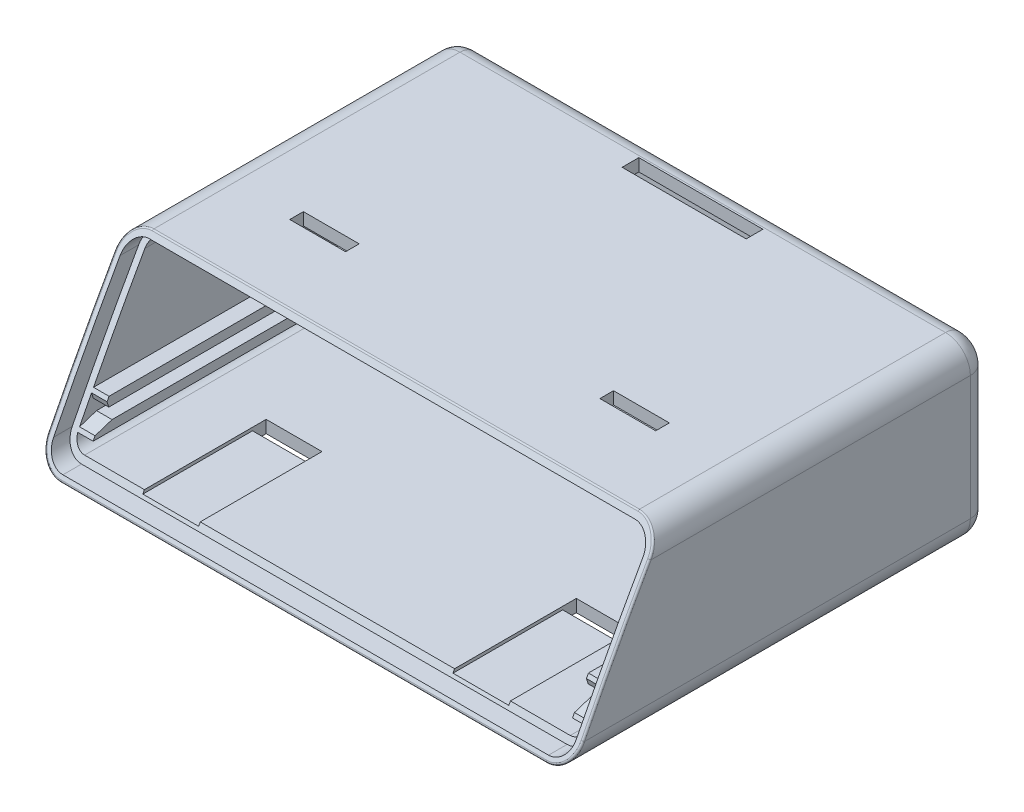
SolidWorks part; units mm, degrees
ref_plane "Front Plane" through (0, 0, 0) normal (0, 0, 1) x (1, 0, 0)
ref_plane "Top Plane" through (0, 0, 0) normal (0, 1, 0) x (1, 0, 0)
ref_plane "Right Plane" through (0, 0, 0) normal (1, 0, 0) x (0, 0, -1)
sketch "Sketch1" plane through (0, 0, 0) normal (0, 1, 0) x (1, 0, 0)
  line L1 (-43.14, -33.75) -> (43.14, -33.75)
  line L2 (-43.14, -33.75) -> (-43.14, 33.75)
  line L3 (-43.14, 33.75) -> (43.14, 33.75)
  line L4 (43.14, -33.75) -> (43.14, 33.75)
  line L5 (-43.14, -33.75) -> (43.14, 33.75) construction
  line L6 (-43.14, 33.75) -> (43.14, -33.75) construction
  point P0 (0, 0)
  dimension "D1" = 67.5
  dimension "D2" = 86.28
extrude "Boss-Extrude1" add sketch "Sketch1" along normal blind 28
fillet "Fillet1" radius 4 4 edges at (43.14, 28, 0) (43.14, 0, 0) (-43.14, 0, 0) (-43.14, 28, 0)
shell "Shell1" thickness 2
sketch "Sketch2" plane through (-43.14, 0, 0) normal (-1, 0, 0) x (0, 0, 1)
  line L0 (-33.75, 28) -> (33.75, 28) construction
  line L1 (18.75, 28) -> (33.75, 28)
  line L2 (33.75, 28) -> (33.75, 0)
  arc A0 (33.75, 0) -> (18.75, 28) centre (-392.2189, -210.1797) ccw
  dimension "D1" = 15
  dimension "D2" = 475
extrude "Cut-Extrude1" cut sketch "Sketch2" against normal through all
sketch "Sketch3" plane through (0, 0, -33.75) normal (0, 0, -1) x (-1, 0, 0)
  line L0 (-7.15, 18.7) -> (7.15, 18.7)
  line L1 (-6.95, 18.5) -> (6.95, 18.5) construction
  line L2 (-6.95, 18.5) -> (-6.95, 2.2) construction
  line L3 (-6.95, 2.2) -> (6.95, 2.2) construction
  line L4 (6.95, 18.5) -> (6.95, 2.2) construction
  line L5 (7.15, 18.7) -> (7.15, 2)
  line L6 (-7.15, 2) -> (7.15, 2)
  line L7 (-7.15, 18.7) -> (-7.15, 2)
  line L8 (27.25, 17.2) -> (38.3, 17.2)
  line L9 (27.45, 17) -> (38.1, 17) construction
  line L10 (27.45, 17) -> (27.45, 3.35) construction
  line L11 (27.45, 3.35) -> (38.1, 3.35) construction
  line L12 (38.1, 17) -> (38.1, 3.35) construction
  line L13 (38.3, 17.2) -> (38.3, 3.15)
  line L14 (27.25, 3.15) -> (38.3, 3.15)
  line L15 (27.25, 17.2) -> (27.25, 3.15)
  dimension "D1" = 0.2
  dimension "D2" = 0.2
extrude "Cut-Extrude2" cut sketch "Sketch3" against normal up to surface (2 mm away) up to face at (0, 14, -31.75)
fillet "Fillet2" radius 3 8 edges at (41.9684, 26.8284, -33.75) (43.14, 14, -33.75) (41.9684, 1.1716, -33.75) (0, 0, -33.75) (-41.9684, 1.1716, -33.75) (-43.14, 14, -33.75) (-41.9684, 26.8284, -33.75) (0, 28, -33.75)
sketch "Sketch4" plane through (0, 0, -31.75) normal (0, 0, 1) x (1, 0, 0)
  line L0 (-7.15, 2) -> (7.15, 2)
  line L1 (-7.15, 1) -> (7.15, 1)
  line L2 (7.15, 1) -> (39.14, 1)
  line L3 (42.14, 4) -> (42.14, 24)
  line L4 (39.14, 27) -> (-39.14, 27)
  line L5 (-42.14, 24) -> (-42.14, 4)
  line L6 (-39.14, 1) -> (-7.15, 1)
  line L8 (-7.15, 18.7) -> (7.15, 18.7)
  line L9 (7.15, 18.7) -> (7.15, 2)
  line L10 (7.15, 2) -> (39.14, 2)
  line L11 (41.14, 4) -> (41.14, 24)
  line L12 (39.14, 26) -> (-39.14, 26)
  line L13 (-41.14, 24) -> (-41.14, 4)
  line L14 (-39.14, 2) -> (-7.15, 2)
  line L15 (-7.15, 2) -> (-7.15, 18.7)
  line L18 (7.15, 2) -> (39.14, 2)
  line L19 (41.14, 4) -> (41.14, 24)
  line L20 (39.14, 26) -> (-39.14, 26)
  line L21 (-41.14, 24) -> (-41.14, 4)
  line L22 (-39.14, 2) -> (-7.15, 2)
  arc A0 (39.14, 1) -> (42.14, 4) centre (39.14, 4) ccw
  arc A1 (42.14, 24) -> (39.14, 27) centre (39.14, 24) ccw
  arc A2 (-39.14, 27) -> (-42.14, 24) centre (-39.14, 24) ccw
  arc A3 (-42.14, 4) -> (-39.14, 1) centre (-39.14, 4) ccw
  arc A4 (39.14, 2) -> (41.14, 4) centre (39.14, 4) ccw
  arc A5 (41.14, 24) -> (39.14, 26) centre (39.14, 24) ccw
  arc A6 (-39.14, 26) -> (-41.14, 24) centre (-39.14, 24) ccw
  arc A7 (-41.14, 4) -> (-39.14, 2) centre (-39.14, 4) ccw
  arc A8 (39.14, 2) -> (41.14, 4) centre (39.14, 4) ccw
  arc A9 (41.14, 24) -> (39.14, 26) centre (39.14, 24) ccw
  arc A10 (-39.14, 26) -> (-41.14, 24) centre (-39.14, 24) ccw
  arc A11 (-41.14, 4) -> (-39.14, 2) centre (-39.14, 4) ccw
  dimension "D1" = 0
  dimension "D2" = 1
extrude "Cut-Extrude3" cut sketch "Sketch4" against normal offset from surface (19.4971 mm away) 3 from offset 80
fillet "Fillet3" radius 0.3 8 edges at (41.7842, 27.0013, 19.3272) (43.14, 14.064, 26.517) (41.4452, 0.7311, 33.3885) (0, 0, 33.75) (-42.0581, 1.2642, 33.1239) (-43.14, 14.064, 26.517) (-41.3892, 27.3077, 19.1504) (0, 28, 18.75)
sketch "Sketch5" plane through (0, 0, -31.75) normal (0, 0, 1) x (1, 0, 0)
  line L0 (41.14, 24) -> (41.14, 4) construction
  line L1 (41.14, 5.25) -> (38.64, 5.25)
  line L2 (41.14, 5.25) -> (41.14, 3.75)
  line L3 (41.14, 3.75) -> (38.64, 3.75)
  line L4 (38.64, 5.25) -> (38.64, 3.75)
  line L5 (34.8894, 7.05) -> (40.64, 7.05) construction
  line L6 (41.14, 7.25) -> (38.64, 7.25)
  line L7 (41.14, 7.25) -> (41.14, 8.75)
  line L8 (41.14, 8.75) -> (38.64, 8.75)
  line L9 (38.64, 7.25) -> (38.64, 8.75)
  line L10 (-40.64, 7.05) -> (40.64, 7.05) construction
  line L11 (40.64, 5.45) -> (34.7752, 5.45) construction
  line L12 (-40.64, 5.45) -> (40.64, 5.45) construction
  line L13 (-41.14, 4) -> (-41.14, 24) construction
  line L14 (-41.14, 8.75) -> (-38.64, 8.75)
  line L15 (-41.14, 8.75) -> (-41.14, 7.25)
  line L16 (-41.14, 7.25) -> (-38.64, 7.25)
  line L17 (-38.64, 8.75) -> (-38.64, 7.25)
  line L19 (-41.14, 5.25) -> (-38.64, 5.25)
  line L20 (-41.14, 5.25) -> (-41.14, 3.75)
  line L21 (-41.14, 3.75) -> (-38.64, 3.75)
  line L22 (-38.64, 5.25) -> (-38.64, 3.75)
  dimension "D1" = 0.2
  dimension "D2" = 0.2
  dimension "D3" = 1.5
  dimension "D4" = 2.5
extrude "Boss-Extrude2" add sketch "Sketch5" along normal up to surface (59.8691 mm away)
sketch "Sketch6" plane through (0, 28, 0) normal (0, 1, 0) x (1, 0, 0)
  line L0 (0, 0) -> (0, 30.75) construction
  line L1 (-28.5, -4.33) -> (-28.5, -6.13) construction
  line L2 (21.5, -4.33) -> (28.5, -4.33) construction
  line L3 (21.5, -4.33) -> (21.5, -6.13) construction
  line L4 (21.5, -6.13) -> (28.5, -6.13) construction
  line L5 (28.5, -4.33) -> (28.5, -6.13) construction
  line L6 (20.5, -4.13) -> (29.5, -4.13)
  line L7 (20.5, -4.13) -> (20.5, -6.33)
  line L8 (20.5, -6.33) -> (29.5, -6.33)
  line L9 (39.14, 30.75) -> (-39.14, 30.75) construction
  line L10 (29.5, -4.13) -> (29.5, -6.33)
  line L11 (-21.5, -6.13) -> (-28.5, -6.13) construction
  line L12 (-21.5, -4.33) -> (-21.5, -6.13) construction
  line L13 (-21.5, -4.33) -> (-28.5, -4.33) construction
  line L14 (-29.5, -4.13) -> (-29.5, -6.33)
  line L15 (-20.5, -6.33) -> (-29.5, -6.33)
  line L16 (-20.5, -4.13) -> (-20.5, -6.33)
  line L17 (-20.5, -4.13) -> (-29.5, -4.13)
  dimension "D1" = 0.2
  dimension "D2" = 0.2
  dimension "D3" = 1
  dimension "D4" = 1
extrude "Cut-Extrude4" cut sketch "Sketch6" against normal up to surface (2 mm away) up to face at (0, 26, -7.4237)
sketch "Sketch9" plane through (0, 0, 0) normal (0, -1, 0) x (1, 0, 0)
  line L0 (0, 0) -> (0, -33.75) construction
  line L1 (-21.5, 12.13) -> (-28.5, 12.13) construction
  line L2 (-21.5, 12.13) -> (-21.5, 10.33) construction
  line L3 (-21.5, 10.33) -> (-28.5, 10.33) construction
  line L4 (-28.5, 12.13) -> (-28.5, 10.33) construction
  line L5 (-20.5, 12.33) -> (-29.5, 12.33)
  line L6 (-20.5, 12.33) -> (-20.5, 10.13)
  line L7 (-20.5, 10.13) -> (-29.5, 10.13)
  line L8 (-29.5, 12.33) -> (-29.5, 10.13)
  line L9 (-39.14, -33.75) -> (39.14, -33.75) construction
  line L10 (28.5, 12.13) -> (28.5, 10.33) construction
  line L11 (21.5, 10.33) -> (28.5, 10.33) construction
  line L12 (21.5, 12.13) -> (21.5, 10.33) construction
  line L13 (21.5, 12.13) -> (28.5, 12.13) construction
  line L14 (29.5, 12.33) -> (29.5, 10.13)
  line L15 (20.5, 10.13) -> (29.5, 10.13)
  line L16 (20.5, 12.33) -> (20.5, 10.13)
  line L17 (20.5, 12.33) -> (29.5, 12.33)
  dimension "D1" = 0.2
  dimension "D2" = 0.2
  dimension "D3" = 1
  dimension "D4" = 1
extrude "Cut-Extrude7" cut sketch "Sketch9" against normal up to surface (2 mm away) up to face at (3.9987, 2, -16.6017)
sketch "Sketch7" plane through (0, 28, 0) normal (0, 1, 0) x (1, 0, 0)
  line L0 (-39.14, 33.75) -> (39.14, 33.75) construction
  line L1 (-10, 30.15) -> (10, 30.15)
  line L2 (-10, 30.15) -> (-10, 27.75)
  line L3 (-10, 27.75) -> (10, 27.75)
  line L4 (10, 30.15) -> (10, 27.75)
  line L5 (0, 0) -> (0, 27.75) construction
  dimension "D1" = 3.6
  dimension "D2" = 2.4
  dimension "D3" = 20
extrude "Cut-Extrude5" cut sketch "Sketch7" against normal up to surface (2 mm away) up to face at (-25, 26, 5.23)
sketch "Sketch8" plane through (0, 0, 6.33) normal (0, 0, -1) x (-1, 0, 0)
  line L0 (-29.5, 26) -> (-20.5, 26) construction
  line L1 (-20.5, 26) -> (-20.5, 28) construction
  line L3 (-29.5, 28) -> (-29.5, 26) construction
  line L4 (20.5, 26) -> (29.5, 26)
  line L5 (29.5, 26) -> (29.5, 28)
  line L6 (29.5, 28) -> (20.5, 28)
  line L7 (20.5, 28) -> (20.5, 26)
  line L8 (20.5, 26) -> (29.5, 26)
  line L9 (29.5, 26) -> (29.5, 26.5)
  line L10 (-20.5, 26.5) -> (-29.5, 26.5)
  line L11 (20.5, 26.5) -> (20.5, 26)
  line L20 (-29.5, 26) -> (-20.5, 26)
  line L21 (-20.5, 26) -> (-20.5, 26.5)
  line L23 (-29.5, 26.5) -> (-29.5, 26)
  line L32 (29.5, 26.5) -> (20.5, 26.5)
  dimension "D2" = 0.5
  dimension "D3" = 0.5
  dimension "D1" = 0
extrude "Cut-Extrude6" cut sketch "Sketch8" against normal through all
sketch "Sketch10" plane through (0, 0, 12.33) normal (0, 0, -1) x (-1, 0, 0)
  line L0 (29.5, 1.5) -> (20.5, 1.5)
  line L1 (-20.5, 1.5) -> (-29.5, 1.5)
  line L4 (29.5, 2) -> (20.5, 2)
  line L5 (20.5, 2) -> (20.5, 0)
  line L6 (20.5, 0) -> (29.5, 0)
  line L7 (29.5, 0) -> (29.5, 2)
  line L8 (29.5, 2) -> (20.5, 2)
  line L9 (20.5, 2) -> (20.5, 1.5)
  line L11 (29.5, 1.5) -> (29.5, 2)
  line L12 (-20.5, 2) -> (-29.5, 2)
  line L13 (-29.5, 2) -> (-29.5, 0)
  line L14 (-29.5, 0) -> (-20.5, 0)
  line L15 (-20.5, 0) -> (-20.5, 2)
  line L16 (-20.5, 2) -> (-29.5, 2)
  line L17 (-29.5, 2) -> (-29.5, 1.5)
  line L19 (-20.5, 1.5) -> (-20.5, 2)
  dimension "D3" = 0.5
  dimension "D1" = 0
  dimension "D2" = 0
extrude "Cut-Extrude8" cut sketch "Sketch10" against normal through all
sketch "Sketch11" plane through (0, 0, -31.75) normal (0, 0, 1) x (1, 0, 0)
  line L0 (7.15, 18.7) -> (7.15, 2) construction
  line L1 (-41.14, 5.25) -> (-38.3, 5.25)
  line L2 (-41.14, 5.25) -> (-41.14, 7.25)
  line L3 (-41.14, 7.25) -> (-38.3, 7.25)
  line L4 (41.14, 5.25) -> (41.14, 7.25)
  line L5 (-7.15, 2) -> (-7.15, 18.7) construction
  line L6 (-27.25, 17.2) -> (-27.25, 3.15) construction
  line L7 (-38.3, 3.15) -> (-38.3, 17.2) construction
  line L8 (7.15, 7.25) -> (7.15, 5.25)
  line L9 (-7.15, 5.25) -> (-7.15, 7.25)
  line L10 (-27.25, 7.25) -> (-27.25, 5.25)
  line L11 (-38.3, 5.25) -> (-38.3, 7.25)
  line L12 (-27.25, 5.25) -> (-7.15, 5.25)
  line L13 (-27.25, 7.25) -> (-7.15, 7.25)
  line L14 (7.15, 7.25) -> (41.14, 7.25)
  line L15 (7.15, 5.25) -> (41.14, 5.25)
extrude "Boss-Extrude3" add sketch "Sketch11" along normal blind 0.5
chamfer "Chamfer1" distance 1 angle 45 4 edges at (39.89, 5.25, 28.1191) (39.89, 7.25, 27.0954) (-39.89, 7.25, 27.0954) (-39.89, 5.25, 28.1191)
sketch "Sketch12" plane through (0, 0, -30.15) normal (0, 0, 1) x (1, 0, 0)
  line L4 (10, 26) -> (10, 28)
  line L5 (10, 28) -> (-10, 28)
  line L6 (-10, 28) -> (-10, 26)
  line L7 (-10, 26) -> (10, 26)
  line L8 (10, 26) -> (10, 28)
  line L9 (10, 28) -> (-10, 28)
  line L10 (-10, 28) -> (-10, 26)
  line L11 (-10, 26) -> (10, 26)
  dimension "D1" = 0
extrude "Cut-Extrude9" cut sketch "Sketch12" against normal blind 0.3
